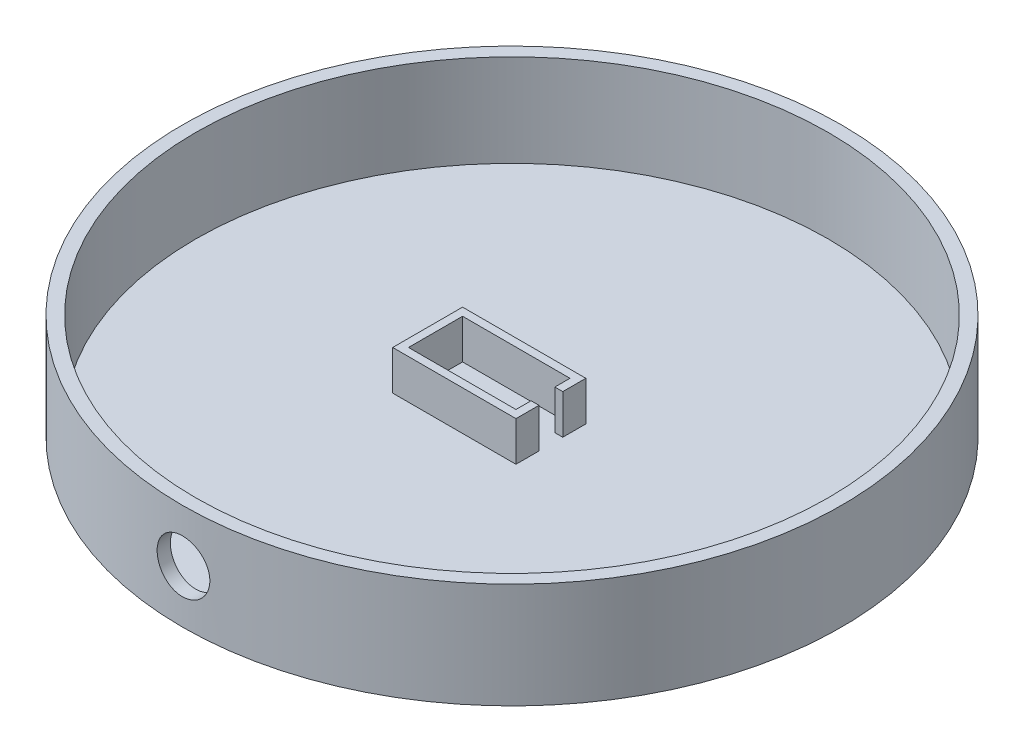
SolidWorks part; units mm, degrees
ref_plane "Front Plane" through (0, 0, 0) normal (0, 0, 1) x (1, 0, 0)
ref_plane "Top Plane" through (0, 0, 0) normal (0, 1, 0) x (1, 0, 0)
ref_plane "Right Plane" through (0, 0, 0) normal (1, 0, 0) x (0, 0, -1)
sketch "Sketch1" plane through (0, 0, 0) normal (0, 1, 0) x (1, 0, 0)
  circle A0 centre (0, 0) radius 125
  dimension "D1" = 250
extrude "Boss-Extrude1" add sketch "Sketch1" along normal blind 40
sketch "Sketch2" plane through (0, 40, 0) normal (0, 1, 0) x (1, 0, 0)
  circle A0 centre (0, 0) radius 120
  dimension "D1" = 240
extrude "Cut-Extrude1" cut sketch "Sketch2" against normal blind 35
sketch "Sketch3" plane through (0, 5, 0) normal (0, 1, 0) x (1, 0, 0)
  line L0 (0, -10.25) -> (0, 10.25) construction
  line L1 (0, 10.25) -> (11.75, 10.25)
  line L2 (11.75, 10.25) -> (11.75, -10.25)
  line L3 (11.75, -10.25) -> (0, -10.25)
  line L4 (0, -10.25) -> (-29, -10.25)
  line L5 (-29, -10.25) -> (-29, 10.25)
  line L6 (-29, 10.25) -> (0, 10.25)
  line L7 (14.75, 13.25) -> (14.75, -13.25)
  line L8 (14.75, -13.25) -> (-32, -13.25)
  line L9 (-32, -13.25) -> (-32, 13.25)
  line L10 (-32, 13.25) -> (14.75, 13.25)
  point P3 (0, 0)
  dimension "D1" = 20.5
  dimension "D2" = 11.75
  dimension "D3" = 29
  dimension "D4" = 3
  dimension "D5" = 3
  dimension "D6" = 3
  dimension "D7" = 3
extrude "Boss-Extrude2" add sketch "Sketch3" along normal blind 15
sketch "Sketch4" plane through (0, 20, 0) normal (0, 1, 0) x (1, 0, 0)
  line L0 (11.75, 4.5) -> (14.75, 4.5)
  line L1 (11.75, -10.25) -> (11.75, 10.25) construction
  line L2 (14.75, -13.25) -> (14.75, 13.25) construction
  line L3 (14.75, 4.5) -> (14.75, -4.5)
  line L4 (14.75, -13.25) -> (14.75, 13.25) construction
  line L5 (14.75, -4.5) -> (11.75, -4.5)
  line L6 (11.75, -4.5) -> (11.75, 4.5)
  point P6 (14.75, 0)
  point P11 (14.75, 0)
  dimension "D1" = 9
extrude "Cut-Extrude2" cut sketch "Sketch4" against normal blind 15
sketch "Sketch7" plane through (0, 0, 13.25) normal (0, 0, 1) x (1, 0, 0)
  line L0 (0, 40) -> (0, 0) construction
  line L1 (125, 40) -> (-125, 40) construction
  circle A0 centre (0, 20) radius 10
  point P8 (0, 20)
  dimension "D1" = 20
extrude "Cut-Extrude3" cut sketch "Sketch7" along normal blind 193
